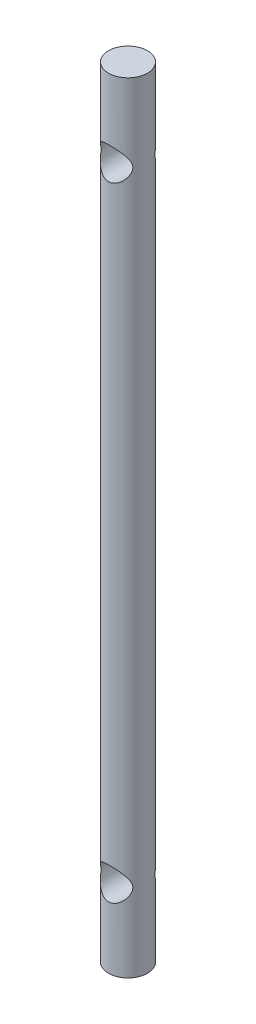
SolidWorks part; units mm, degrees
ref_plane "Front Plane" through (0, 0, 0) normal (0, 0, 1) x (1, 0, 0)
ref_plane "Top Plane" through (0, 0, 0) normal (0, 1, 0) x (1, 0, 0)
ref_plane "Right Plane" through (0, 0, 0) normal (1, 0, 0) x (0, 0, -1)
sketch "Sketch1" plane through (0, 0, 0) normal (0, 1, 0) x (1, 0, 0)
  circle A0 centre (0, 0) radius 3.175
  dimension "D1" = 6.35
extrude "Boss-Extrude1" add sketch "Sketch1" along normal blind 127
sketch "Sketch2" plane through (0, 0, 0) normal (0, 0, 1) x (1, 0, 0)
  line L0 (3.175, 127) -> (-3.175, 127) construction
  circle A0 centre (0, 114.3) radius 2.6035
  circle A1 centre (0, 12.7) radius 2.6035
  dimension "D1" = 5.207
  dimension "D3" = 5.207
  dimension "D2" = 12.7
  dimension "D4" = 12.7
extrude "Cut-Extrude1" cut sketch "Sketch2" against normal blind 127 and the other way blind 127
